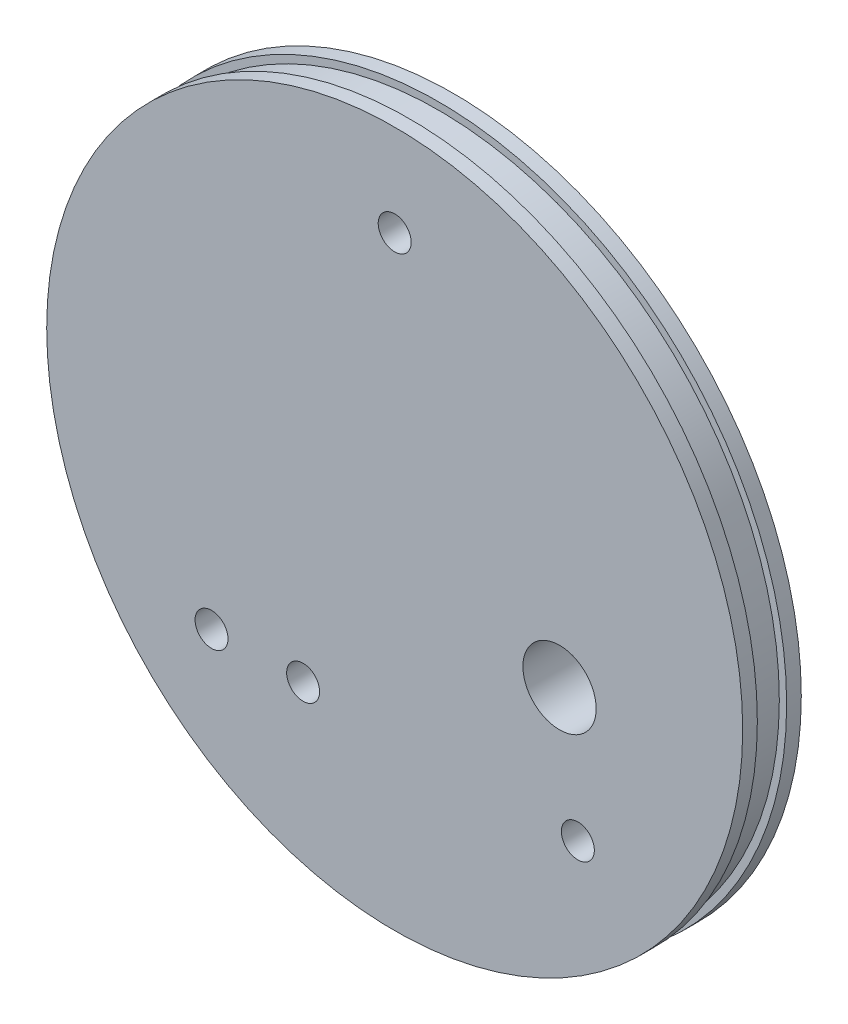
SolidWorks part; units mm, degrees
ref_plane "Front Plane" through (0, 0, 0) normal (0, 0, 1) x (1, 0, 0)
ref_plane "Top Plane" through (0, 0, 0) normal (0, 1, 0) x (1, 0, 0)
ref_plane "Right Plane" through (0, 0, 0) normal (1, 0, 0) x (0, 0, -1)
sketch "Sketch2" plane through (0, 0, 0) normal (0, 0, 1) x (1, 0, 0)
  circle A0 centre (0, 0) radius 93
  circle A1 centre (0, 0) radius 95
  dimension "D1" = 186
  dimension "D2" = 190
extrude "Boss-Extrude1" add sketch "Sketch2" along normal blind 8 and the other way blind 8 contours A1 A0 | A0 region at (-94.7313, 0, 0)
extrude "Cut-Extrude1" cut sketch "Sketch2<5>" against normal blind 4 and the other way blind 4
sketch "Sketch2<5>" plane through (0, 0, 0) normal (0, 0, 1) x (1, 0, 0) same geometry as "Sketch2"
sketch "Sketch3" plane through (0, 0, 8) normal (0, 0, 1) x (1, 0, 0)
  line L0 (0, 33.75) -> (0, -33.75) construction
  line L1 (41.5, 33.75) -> (-78.5, 33.75)
  line L2 (41.5, 33.75) -> (41.5, -33.75)
  line L3 (41.5, -33.75) -> (-78.5, -33.75) construction
  line L4 (-78.5, 33.75) -> (-78.5, -33.75) construction
  line L5 (31, 33.75) -> (31, -33.75) construction
  line L6 (41.5, 0) -> (-78.5, 0) construction
  line L7 (-78.5, 28.75) -> (-43.5, 28.75)
  line L8 (-43.5, 28.75) -> (-43.5, -33.75)
  line L9 (-78.5, 33.75) -> (-78.5, 28.75)
  line L10 (-43.5, -33.75) -> (41.5, -33.75)
  circle A0 centre (0, 0) radius 31
  circle A1 centre (0, 0) radius 33.75
  point P9 (0, 0)
  dimension "D3" = 62
  dimension "D7" = 67.5
  dimension "D1" = 10.5
  dimension "D2" = 120
  dimension "D4" = 67.5
  dimension "D5" = 5
  dimension "D6" = 35
sketch "Sketch4" plane through (0, 0, -8) normal (0, 0, 1) x (1, 0, 0)
  line L0 (0, 33.75) -> (0, -33.75) construction
  line L1 (41.5, 33.75) -> (-78.5, 33.75)
  line L2 (41.5, 33.75) -> (41.5, -33.75)
  line L3 (41.5, -33.75) -> (-78.5, -33.75) construction
  line L4 (-78.5, 33.75) -> (-78.5, -33.75) construction
  line L5 (31, 33.75) -> (31, -33.75) construction
  line L6 (41.5, 0) -> (-78.5, 0) construction
  line L7 (-78.5, 28.75) -> (-43.5, 28.75)
  line L8 (-43.5, 28.75) -> (-43.5, -33.75)
  line L9 (-78.5, 33.75) -> (-78.5, 28.75)
  line L10 (-43.5, -33.75) -> (41.5, -33.75)
  circle A0 centre (0, 0) radius 31
  point P9 (0, 0)
  dimension "D3" = 62
  dimension "D1" = 10.5
  dimension "D2" = 120
  dimension "D4" = 67.5
  dimension "D5" = 5
  dimension "D6" = 35
ref_plane "Plane1" through (0, -33.75, 0) normal (0, 1, 0) x (1, 0, 0)
sketch "Sketch7" plane through (0, 0, 8) normal (0, 0, 1) x (1, 0, 0)
  line L0 (0, -33.75) -> (0, -48.75) construction
  line L1 (-50, -48.75) -> (50, -48.75) construction
  line L2 (0, -48.75) -> (20, -48.75) construction
  line L3 (0, -48.75) -> (3.6347, -48.75) construction
  circle A0 centre (-50, -48.75) radius 4.5
  circle A1 centre (50, -48.75) radius 4.5
  circle A5 centre (-25, -48.75) radius 4.5
  point P7 (0, -48.75)
  dimension "D3" = 9
  dimension "D4" = 9
  dimension "D7" = 25
  dimension "D6" = 9
  dimension "D1" = 100
  dimension "D2" = 15
extrude "Cut-Extrude2" cut sketch "Sketch7" against normal blind 167
sketch "Sketch10" plane through (0, 0, -8) normal (0, 0, -1) x (-1, 0, 0)
  line L0 (0, 0) -> (0, 70) construction
  circle A0 centre (0, 70) radius 4.5
  circle A1 centre (0, 70) radius 6
  dimension "D2" = 9
  dimension "D3" = 12
  dimension "D1" = 70
extrude "Cut-Extrude4" cut sketch "Sketch10" against normal blind 60 and the other way blind 112 contours A0 region at (0, 70, -8)
sketch "Sketch11" plane through (0, 0, -8) normal (0, 0, -1) x (-1, 0, 0)
  line L0 (0, 0) -> (0, -15) construction
  line L1 (0, -15) -> (-45, -15) construction
  circle A0 centre (-45, -15) radius 10
  dimension "D3" = 20
  dimension "D1" = 15
  dimension "D2" = 45
extrude "Cut-Extrude5" cut sketch "Sketch11" against normal blind 60 contours A0
